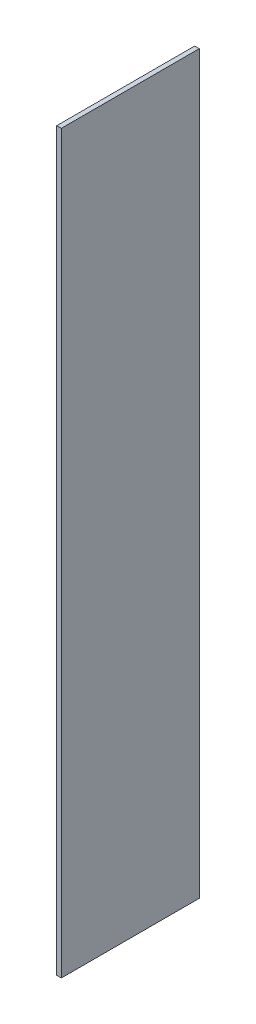
SolidWorks part; units mm, degrees
ref_plane "Front Plane" through (0, 0, 0) normal (0, 0, 1) x (1, 0, 0)
ref_plane "Top Plane" through (0, 0, 0) normal (0, 1, 0) x (1, 0, 0)
ref_plane "Right Plane" through (0, 0, 0) normal (1, 0, 0) x (0, 0, -1)
sketch "Sketch1" plane through (0, 0, 0) normal (0, 0, 1) x (1, 0, 0)
  line L1 (0, 0) -> (0.1, 0)
  line L2 (0, 0) -> (0, 16)
  line L3 (0, 16) -> (0.1, 16)
  line L4 (0.1, 0) -> (0.1, 16)
  dimension "D1" = 16
  dimension "D2" = 0.1
extrude "Boss-Extrude1" add sketch "Sketch1" along normal blind 3
equation "\"A.L\"= 0.06m"
equation "\"A.h\"= 0.005m"
equation "\"A.d\"= 0.003m"
equation "\"A.delta\"= 45.0001"
equation "\"A.w\"= 0.02m"
equation "\"A.v\"= 0.03m"
equation "\"A.s\"= 0.0075m"
equation "\"A.t\"= 0.005m"
equation "\"B.L\"= 0.04m"
equation "\"B.h\"= 0.004m"
equation "\"B.s\"= 0.008m"
equation "\"B.t\"= 0.004m"
equation "\"C.h\"= 0.0062m"
equation "\"C.d\"= 0.003m"
equation "\"C.L\"= 0.05m"
equation "\"C.wmax\"= 0.005m"
equation "\"D.L\"= 0.045m"
equation "\"D.h\"= 0.004m"
equation "\"D.s\"= 0.01m"
equation "\"D.t\"= 0.004m"
equation "\"a_h\"= 0.0001m"
equation "\"a_d\"= 0.003m"
equation "\"a_L\"= 0.01m"
equation "\"b_h\"= 0.0004m"
equation "\"b_d\"= 0.003m"
equation "\"b_L\"= 0.01m"
equation "\"c_h\"= 0.0001m"
equation "\"c_d\"= 0.003m"
equation "\"c_L\"= 0.01m"
equation "\"d_h\"= 0.0001m"
equation "\"d_d\"= 0.003m"
equation "\"d_L\"= 0.01m"
equation "\"S.h\"= 0.015m"
equation "\"S.L\"= 0.0559m"
equation "\"D1@Sketch1\"=\"a_L\"+0.006"
equation "\"D2@Sketch1\"=\"a_h\""
equation "\"D1@Boss-Extrude1\"=\"a_d\""
